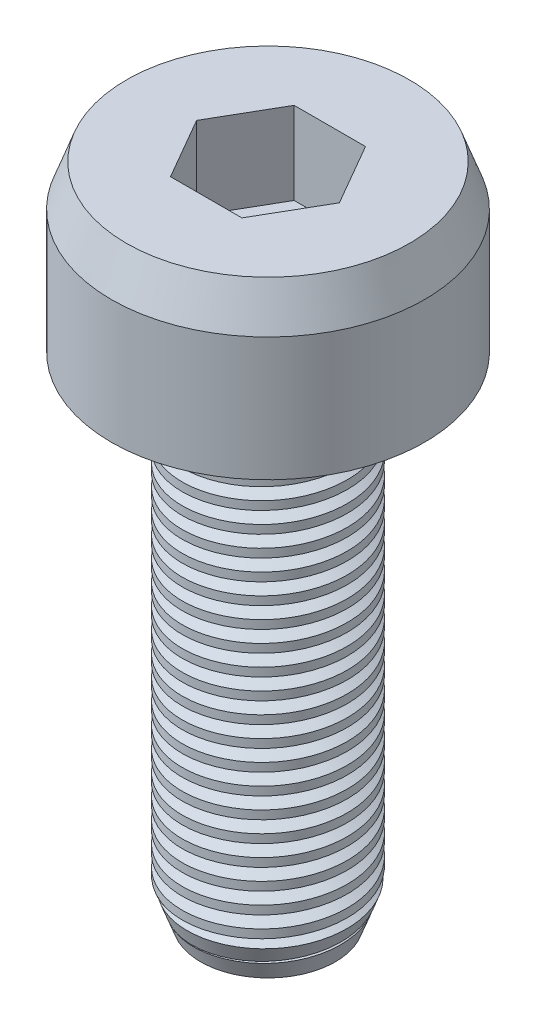
SolidWorks part; units mm, degrees
ref_plane "Front Plane" through (0, 0, 0) normal (0, 0, 1) x (1, 0, 0)
ref_plane "Top Plane" through (0, 0, 0) normal (0, 1, 0) x (1, 0, 0)
ref_plane "Right Plane" through (0, 0, 0) normal (1, 0, 0) x (0, 0, -1)
sketch "Sketch3" plane through (0, 0, 0) normal (0, 1, 0) x (1, 0, 0)
  circle A0 centre (0, 0) radius 1.9
extrude "Boss-Extrude3" add sketch "Sketch3" along normal blind 1.5
sketch "Sketch4" plane through (0, 1.5, 0) normal (0, 1, 0) x (1, 0, 0)
  circle A0 centre (0, 0) radius 1.9
extrude "Boss-Extrude5" add sketch "Sketch4" along normal blind 0.5 draft 20
sketch "Sketch6" plane through (0, 2, 0) normal (0, 1, 0) x (1, 0, 0)
  line L1 (0.866, 0) -> (0.433, 0.75)
  line L2 (0.433, 0.75) -> (-0.433, 0.75)
  line L3 (-0.433, 0.75) -> (-0.866, 0)
  line L4 (-0.866, 0) -> (-0.433, -0.75)
  line L5 (-0.433, -0.75) -> (0.433, -0.75)
  line L6 (0.433, -0.75) -> (0.866, 0)
  circle A0 centre (0, 0) radius 0.75 construction
extrude "Cut-Extrude1" cut sketch "Sketch6" against normal blind 1
sketch "Sketch7" plane through (0, 0, 0) normal (0, -1, 0) x (1, 0, 0)
  circle A0 centre (0, 0) radius 1
extrude "Boss-Extrude6" add sketch "Sketch7" along normal blind 5.5
sketch "Sketch8" plane through (0, -5.5, 0) normal (0, -1, 0) x (1, 0, 0)
  circle A0 centre (0, 0) radius 1
extrude "Boss-Extrude7" add sketch "Sketch8" along normal blind 0.5 draft 20
sketch "Sketch9" plane through (0, -6, 0) normal (0, -1, 0) x (1, 0, 0)
  circle A0 centre (0, 0) radius 1
curve "Helix/Spiral1" pitch 0.25 height 6 turns 24
sketch "Sketch10" plane through (0, 0, 0) normal (0, 0, 1) x (1, 0, 0)
  line L1 (1.0635, -6.11) -> (0.873, -6)
  line L2 (0.873, -6) -> (1.0635, -5.89)
  line L3 (1.0635, -5.89) -> (1.0635, -6.11)
  circle A0 centre (1, -6) radius 0.0635 construction
  spline S0 degree 3 poles (1, -6) (1, -5.9948) (0.9479, -5.9844) (0.7255, -5.9688) (0.3926, -5.9531) (0, -5.9375) (-0.3926, -5.9219) (-0.7255, -5.9063) (-0.9479, -5.8906) (-1.026, -5.875) (-0.9479, -5.8594) (-0.7255, -5.8438) (-0.3926, -5.8281) (0, -5.8125) (0.3926, -5.7969) (0.7255, -5.7813) (0.9479, -5.7656) (1.026, -5.75) (0.9479, -5.7344) (0.7255, -5.7188) (0.3926, -5.7031) (0, -5.6875) (-0.3926, -5.6719) (-0.7255, -5.6562) (-0.9479, -5.6406) (-1.026, -5.625) (-0.9479, -5.6094) (-0.7255, -5.5938) (-0.3926, -5.5781) (0, -5.5625) (0.3926, -5.5469) (0.7255, -5.5313) (0.9479, -5.5156) (1.026, -5.5) (0.9479, -5.4844) (0.7255, -5.4688) (0.3926, -5.4531) (0, -5.4375) (-0.3926, -5.4219) (-0.7255, -5.4062) (-0.9479, -5.3906) (-1.026, -5.375) (-0.9479, -5.3594) (-0.7255, -5.3437) (-0.3926, -5.3281) (0, -5.3125) (0.3926, -5.2969) (0.7255, -5.2812) (0.9479, -5.2656) (1.026, -5.25) (0.9479, -5.2344) (0.7255, -5.2188) (0.3926, -5.2031) (0, -5.1875) (-0.3926, -5.1719) (-0.7255, -5.1562) (-0.9479, -5.1406) (-1.026, -5.125) (-0.9479, -5.1094) (-0.7255, -5.0937) (-0.3926, -5.0781) (0, -5.0625) (0.3926, -5.0469) (0.7255, -5.0312) (0.9479, -5.0156) (1.026, -5) (0.9479, -4.9844) (0.7255, -4.9687) (0.3926, -4.9531) (0, -4.9375) (-0.3926, -4.9219) (-0.7255, -4.9062) (-0.9479, -4.8906) (-1.026, -4.875) (-0.9479, -4.8594) (-0.7255, -4.8437) (-0.3926, -4.8281) (0, -4.8125) (0.3926, -4.7969) (0.7255, -4.7812) (0.9479, -4.7656) (1.026, -4.75) (0.9479, -4.7344) (0.7255, -4.7187) (0.3926, -4.7031) (0, -4.6875) (-0.3926, -4.6719) (-0.7255, -4.6562) (-0.9479, -4.6406) (-1.026, -4.625) (-0.9479, -4.6094) (-0.7255, -4.5937) (-0.3926, -4.5781) (0, -4.5625) (0.3926, -4.5469) (0.7255, -4.5312) (0.9479, -4.5156) (1.026, -4.5) (0.9479, -4.4844) (0.7255, -4.4687) (0.3926, -4.4531) (0, -4.4375) (-0.3926, -4.4219) (-0.7255, -4.4062) (-0.9479, -4.3906) (-1.026, -4.375) (-0.9479, -4.3594) (-0.7255, -4.3437) (-0.3926, -4.3281) (0, -4.3125) (0.3926, -4.2969) (0.7255, -4.2812) (0.9479, -4.2656) (1.026, -4.25) (0.9479, -4.2344) (0.7255, -4.2187) (0.3926, -4.2031) (0, -4.1875) (-0.3926, -4.1719) (-0.7255, -4.1562) (-0.9479, -4.1406) (-1.026, -4.125) (-0.9479, -4.1094) (-0.7255, -4.0937) (-0.3926, -4.0781) (0, -4.0625) (0.3926, -4.0469) (0.7255, -4.0312) (0.9479, -4.0156) (1.026, -4) (0.9479, -3.9844) (0.7255, -3.9687) (0.3926, -3.9531) (0, -3.9375) (-0.3926, -3.9219) (-0.7255, -3.9062) (-0.9479, -3.8906) (-1.026, -3.875) (-0.9479, -3.8594) (-0.7255, -3.8437) (-0.3926, -3.8281) (0, -3.8125) (0.3926, -3.7969) (0.7255, -3.7812) (0.9479, -3.7656) (1.026, -3.75) (0.9479, -3.7344) (0.7255, -3.7187) (0.3926, -3.7031) (0, -3.6875) (-0.3926, -3.6719) (-0.7255, -3.6562) (-0.9479, -3.6406) (-1.026, -3.625) (-0.9479, -3.6094) (-0.7255, -3.5937) (-0.3926, -3.5781) (0, -3.5625) (0.3926, -3.5469) (0.7255, -3.5312) (0.9479, -3.5156) (1.026, -3.5) (0.9479, -3.4844) (0.7255, -3.4687) (0.3926, -3.4531) (0, -3.4375) (-0.3926, -3.4219) (-0.7255, -3.4062) (-0.9479, -3.3906) (-1.026, -3.375) (-0.9479, -3.3594) (-0.7255, -3.3437) (-0.3926, -3.3281) (0, -3.3125) (0.3926, -3.2969) (0.7255, -3.2812) (0.9479, -3.2656) (1.026, -3.25) (0.9479, -3.2344) (0.7255, -3.2187) (0.3926, -3.2031) (0, -3.1875) (-0.3926, -3.1719) (-0.7255, -3.1562) (-0.9479, -3.1406) (-1.026, -3.125) (-0.9479, -3.1094) (-0.7255, -3.0937) (-0.3926, -3.0781) (0, -3.0625) (0.3926, -3.0469) (0.7255, -3.0312) (0.9479, -3.0156) (1.026, -3) (0.9479, -2.9844) (0.7255, -2.9687) (0.3926, -2.9531) (0, -2.9375) (-0.3926, -2.9219) (-0.7255, -2.9062) (-0.9479, -2.8906) (-1.026, -2.875) (-0.9479, -2.8594) (-0.7255, -2.8437) (-0.3926, -2.8281) (0, -2.8125) (0.3926, -2.7969) (0.7255, -2.7812) (0.9479, -2.7656) (1.026, -2.75) (0.9479, -2.7344) (0.7255, -2.7187) (0.3926, -2.7031) (0, -2.6875) (-0.3926, -2.6719) (-0.7255, -2.6562) (-0.9479, -2.6406) (-1.026, -2.625) (-0.9479, -2.6094) (-0.7255, -2.5937) (-0.3926, -2.5781) (0, -2.5625) (0.3926, -2.5469) (0.7255, -2.5312) (0.9479, -2.5156) (1.026, -2.5) (0.9479, -2.4844) (0.7255, -2.4687) (0.3926, -2.4531) (0, -2.4375) (-0.3926, -2.4219) (-0.7255, -2.4062) (-0.9479, -2.3906) (-1.026, -2.375) (-0.9479, -2.3594) (-0.7255, -2.3437) (-0.3926, -2.3281) (0, -2.3125) (0.3926, -2.2969) (0.7255, -2.2812) (0.9479, -2.2656) (1.026, -2.25) (0.9479, -2.2344) (0.7255, -2.2187) (0.3926, -2.2031) (0, -2.1875) (-0.3926, -2.1719) (-0.7255, -2.1562) (-0.9479, -2.1406) (-1.026, -2.125) (-0.9479, -2.1094) (-0.7255, -2.0937) (-0.3926, -2.0781) (0, -2.0625) (0.3926, -2.0469) (0.7255, -2.0312) (0.9479, -2.0156) (1.026, -2) (0.9479, -1.9844) (0.7255, -1.9687) (0.3926, -1.9531) (0, -1.9375) (-0.3926, -1.9219) (-0.7255, -1.9062) (-0.9479, -1.8906) (-1.026, -1.875) (-0.9479, -1.8594) (-0.7255, -1.8437) (-0.3926, -1.8281) (0, -1.8125) (0.3926, -1.7969) (0.7255, -1.7812) (0.9479, -1.7656) (1.026, -1.75) (0.9479, -1.7344) (0.7255, -1.7187) (0.3926, -1.7031) (0, -1.6875) (-0.3926, -1.6719) (-0.7255, -1.6562) (-0.9479, -1.6406) (-1.026, -1.625) (-0.9479, -1.6094) (-0.7255, -1.5937) (-0.3926, -1.5781) (0, -1.5625) (0.3926, -1.5469) (0.7255, -1.5312) (0.9479, -1.5156) (1.026, -1.5) (0.9479, -1.4844) (0.7255, -1.4687) (0.3926, -1.4531) (0, -1.4375) (-0.3926, -1.4219) (-0.7255, -1.4062) (-0.9479, -1.3906) (-1.026, -1.375) (-0.9479, -1.3594) (-0.7255, -1.3437) (-0.3926, -1.3281) (0, -1.3125) (0.3926, -1.2969) (0.7255, -1.2812) (0.9479, -1.2656) (1.026, -1.25) (0.9479, -1.2344) (0.7255, -1.2187) (0.3926, -1.2031) (0, -1.1875) (-0.3926, -1.1719) (-0.7255, -1.1562) (-0.9479, -1.1406) (-1.026, -1.125) (-0.9479, -1.1094) (-0.7255, -1.0937) (-0.3926, -1.0781) (0, -1.0625) (0.3926, -1.0469) (0.7255, -1.0312) (0.9479, -1.0156) (1.026, -1) (0.9479, -0.9844) (0.7255, -0.9687) (0.3926, -0.9531) (0, -0.9375) (-0.3926, -0.9219) (-0.7255, -0.9062) (-0.9479, -0.8906) (-1.026, -0.875) (-0.9479, -0.8594) (-0.7255, -0.8437) (-0.3926, -0.8281) (0, -0.8125) (0.3926, -0.7969) (0.7255, -0.7812) (0.9479, -0.7656) (1.026, -0.75) (0.9479, -0.7344) (0.7255, -0.7187) (0.3926, -0.7031) (0, -0.6875) (-0.3926, -0.6719) (-0.7255, -0.6562) (-0.9479, -0.6406) (-1.026, -0.625) (-0.9479, -0.6094) (-0.7255, -0.5937) (-0.3926, -0.5781) (0, -0.5625) (0.3926, -0.5469) (0.7255, -0.5312) (0.9479, -0.5156) (1.026, -0.5) (0.9479, -0.4844) (0.7255, -0.4687) (0.3926, -0.4531) (0, -0.4375) (-0.3926, -0.4219) (-0.7255, -0.4062) (-0.9479, -0.3906) (-1.026, -0.375) (-0.9479, -0.3594) (-0.7255, -0.3437) (-0.3926, -0.3281) (0, -0.3125) (0.3926, -0.2969) (0.7255, -0.2812) (0.9479, -0.2656) (1.026, -0.25) (0.9479, -0.2344) (0.7255, -0.2187) (0.3926, -0.2031) (0, -0.1875) (-0.3926, -0.1719) (-0.7255, -0.1562) (-0.9479, -0.1406) (-1.026, -0.125) (-0.9479, -0.1094) (-0.7255, -0.0937) (-0.3926, -0.0781) (0, -0.0625) (0.3926, -0.0469) (0.7255, -0.0312) (0.9479, -0.0156) (1, -0.0052) (1, 0) knots 0 0 0 0 0.002604 0.005208 0.007812 0.010417 0.013021 0.015625 0.018229 0.020833 0.023437 0.026042 0.028646 0.03125 0.033854 0.036458 0.039062 0.041667 0.044271 0.046875 0.049479 0.052083 0.054687 0.057292 0.059896 0.0625 0.065104 0.067708 0.070312 0.072917 0.075521 0.078125 0.080729 0.083333 0.085937 0.088542 0.091146 0.09375 0.096354 0.098958 0.101562 0.104167 0.106771 0.109375 0.111979 0.114583 0.117187 0.119792 0.122396 0.125 0.127604 0.130208 0.132812 0.135417 0.138021 0.140625 0.143229 0.145833 0.148437 0.151042 0.153646 0.15625 0.158854 0.161458 0.164062 0.166667 0.169271 0.171875 0.174479 0.177083 0.179687 0.182292 0.184896 0.1875 0.190104 0.192708 0.195312 0.197917 0.200521 0.203125 0.205729 0.208333 0.210937 0.213542 0.216146 0.21875 0.221354 0.223958 0.226562 0.229167 0.231771 0.234375 0.236979 0.239583 0.242187 0.244792 0.247396 0.25 0.252604 0.255208 0.257812 0.260417 0.263021 0.265625 0.268229 0.270833 0.273437 0.276042 0.278646 0.28125 0.283854 0.286458 0.289062 0.291667 0.294271 0.296875 0.299479 0.302083 0.304687 0.307292 0.309896 0.3125 0.315104 0.317708 0.320312 0.322917 0.325521 0.328125 0.330729 0.333333 0.335937 0.338542 0.341146 0.34375 0.346354 0.348958 0.351562 0.354167 0.356771 0.359375 0.361979 0.364583 0.367187 0.369792 0.372396 0.375 0.377604 0.380208 0.382812 0.385417 0.388021 0.390625 0.393229 0.395833 0.398437 0.401042 0.403646 0.40625 0.408854 0.411458 0.414062 0.416667 0.419271 0.421875 0.424479 0.427083 0.429687 0.432292 0.434896 0.4375 0.440104 0.442708 0.445312 0.447917 0.450521 0.453125 0.455729 0.458333 0.460937 0.463542 0.466146 0.46875 0.471354 0.473958 0.476562 0.479167 0.481771 0.484375 0.486979 0.489583 0.492187 0.494792 0.497396 0.5 0.502604 0.505208 0.507812 0.510417 0.513021 0.515625 0.518229 0.520833 0.523437 0.526042 0.528646 0.53125 0.533854 0.536458 0.539062 0.541667 0.544271 0.546875 0.549479 0.552083 0.554687 0.557292 0.559896 0.5625 0.565104 0.567708 0.570312 0.572917 0.575521 0.578125 0.580729 0.583333 0.585937 0.588542 0.591146 0.59375 0.596354 0.598958 0.601562 0.604167 0.606771 0.609375 0.611979 0.614583 0.617187 0.619792 0.622396 0.625 0.627604 0.630208 0.632812 0.635417 0.638021 0.640625 0.643229 0.645833 0.648437 0.651042 0.653646 0.65625 0.658854 0.661458 0.664062 0.666667 0.669271 0.671875 0.674479 0.677083 0.679687 0.682292 0.684896 0.6875 0.690104 0.692708 0.695312 0.697917 0.700521 0.703125 0.705729 0.708333 0.710937 0.713542 0.716146 0.71875 0.721354 0.723958 0.726562 0.729167 0.731771 0.734375 0.736979 0.739583 0.742187 0.744792 0.747396 0.75 0.752604 0.755208 0.757812 0.760417 0.763021 0.765625 0.768229 0.770833 0.773437 0.776042 0.778646 0.78125 0.783854 0.786458 0.789062 0.791667 0.794271 0.796875 0.799479 0.802083 0.804687 0.807292 0.809896 0.8125 0.815104 0.817708 0.820312 0.822917 0.825521 0.828125 0.830729 0.833333 0.835937 0.838542 0.841146 0.84375 0.846354 0.848958 0.851562 0.854167 0.856771 0.859375 0.861979 0.864583 0.867187 0.869792 0.872396 0.875 0.877604 0.880208 0.882812 0.885417 0.888021 0.890625 0.893229 0.895833 0.898437 0.901042 0.903646 0.90625 0.908854 0.911458 0.914062 0.916667 0.919271 0.921875 0.924479 0.927083 0.929687 0.932292 0.934896 0.9375 0.940104 0.942708 0.945312 0.947917 0.950521 0.953125 0.955729 0.958333 0.960938 0.963542 0.966146 0.96875 0.971354 0.973958 0.976562 0.979167 0.981771 0.984375 0.986979 0.989583 0.992188 0.994792 0.997396 1 1 1 1 construction
  dimension "D1" = 0.22
sweep "Cut-Sweep1" cut profiles "Sketch10" path "Helix/Spiral1"
